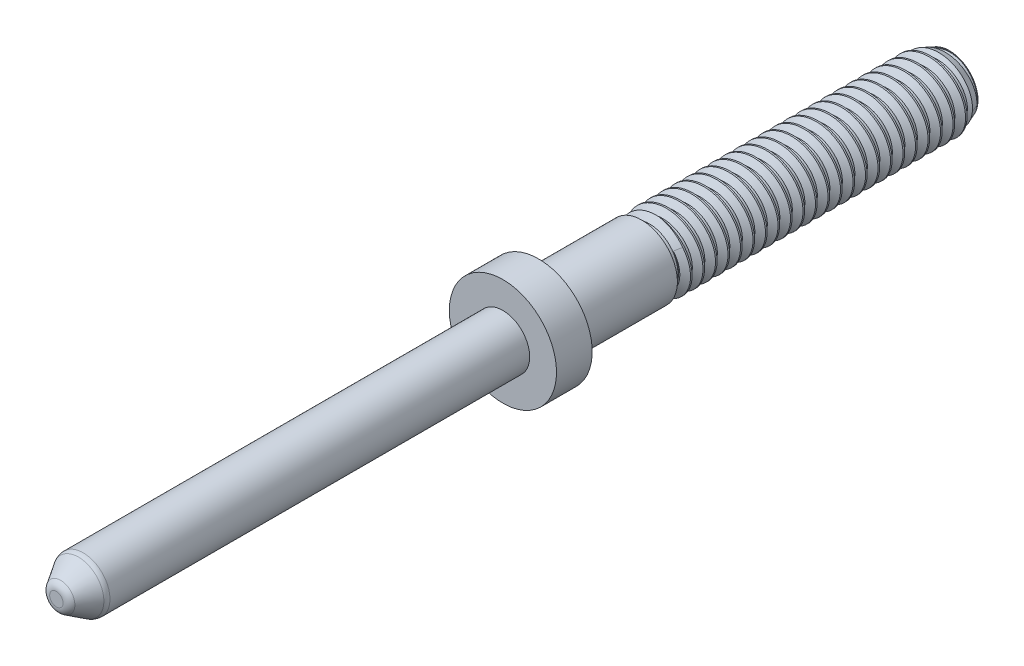
SolidWorks part; units mm, degrees
material "1060 Сплав"
ref_plane "Front" through (0, 0, 0) normal (0, 0, 1) x (1, 0, 0)
ref_plane "Top" through (0, 0, 0) normal (0, 1, 0) x (1, 0, 0)
ref_plane "Right" through (0, 0, 0) normal (1, 0, 0) x (0, 0, -1)
sketch "Эскиз1" plane through (0, 0, 0) normal (0, 1, 0) x (1, 0, 0)
  line L0 (0, 0) -> (0, -58.1417) construction
  line L1 (0, 0) -> (-1.6, 0)
  line L2 (-1.6, 0) -> (-2, -1)
  line L3 (-2, -1) -> (-2, -23) construction
  line L4 (-2, -23) -> (-3, -23)
  line L5 (-3, -23) -> (-3, -25)
  line L6 (-3, -25) -> (-1.5, -25)
  line L7 (-1.5, -25) -> (-1.5, -48.5)
  line L8 (-1.4242, -48.7647) -> (-0.8, -49.7647)
  line L9 (-0.3758, -50) -> (0, -50)
  line L10 (0, -50) -> (0, 0)
  line L11 (-2, -1) -> (-2, -16.5691)
  line L12 (-2, -16.5691) -> (-1.6, -16.8)
  line L13 (-1.6, -16.8) -> (-1.6, -17)
  line L15 (-2, -17.2309) -> (-2, -23)
  line L16 (-1.6, -17) -> (-2, -17.2309)
  arc A0 (-1.5, -48.5) -> (-1.4242, -48.7647) centre (-1, -48.5) ccw
  arc A1 (-0.8, -49.7647) -> (-0.3758, -50) centre (-0.3758, -49.5) ccw
  point P19 (-1.5, -16.6555)
  point P20 (-1.5, -16.5899)
  point P21 (-1.5, -16.5277)
  point P22 (-1.5, -16.7439)
  dimension "D4" = 0.5
  dimension "D1" = 3
  dimension "D2" = 1.6
  dimension "D3" = 1.5
  dimension "D5" = 2
  dimension "D6" = 2
  dimension "D7" = 6
  dimension "D8" = 23
  dimension "D9" = 50
  dimension "D10" = 3.2
  dimension "D11" = 1
  dimension "D12" = 60
  dimension "D13" = 60
  dimension "D14" = 6
  dimension "D15" = 0.2
revolve "Повернуть1" add sketch "Эскиз1" angle 360 about L0
thread "Резьба1" pitch 0.7 method cut profile "Профиль резьбы1" start angle 0, offset 2, length 0, pitch 0.7, diameter 4
ref_plane "Плоскость1" through (2, 0, -1) normal (0, -1, 0) x (1, 0, 0)
sketch "Профиль резьбы1" plane through (2, 0, -1) normal (0, -1, 0) x (1, 0, 0)
  line L0 (0, 0) -> (0, 0.7) construction
  line L11 (0, 0) -> (0, 0.6125)
  line L12 (0, 0.6125) -> (-0.3789, 0.3937)
  line L13 (-0.3789, 0.3937) -> (-0.3789, 0.2187)
  line L15 (-0.3789, 0.2187) -> (0, 0)
  line L17 (-0.3789, 0.3062) -> (0, 0.3062) construction
  point P2 (0, 0)
  dimension "Pitch" = 0.7
  dimension "Profile_Angle" = 60
  dimension "Profile_Land" = 0.175
  dimension "Profile_Height" = 0.3789
